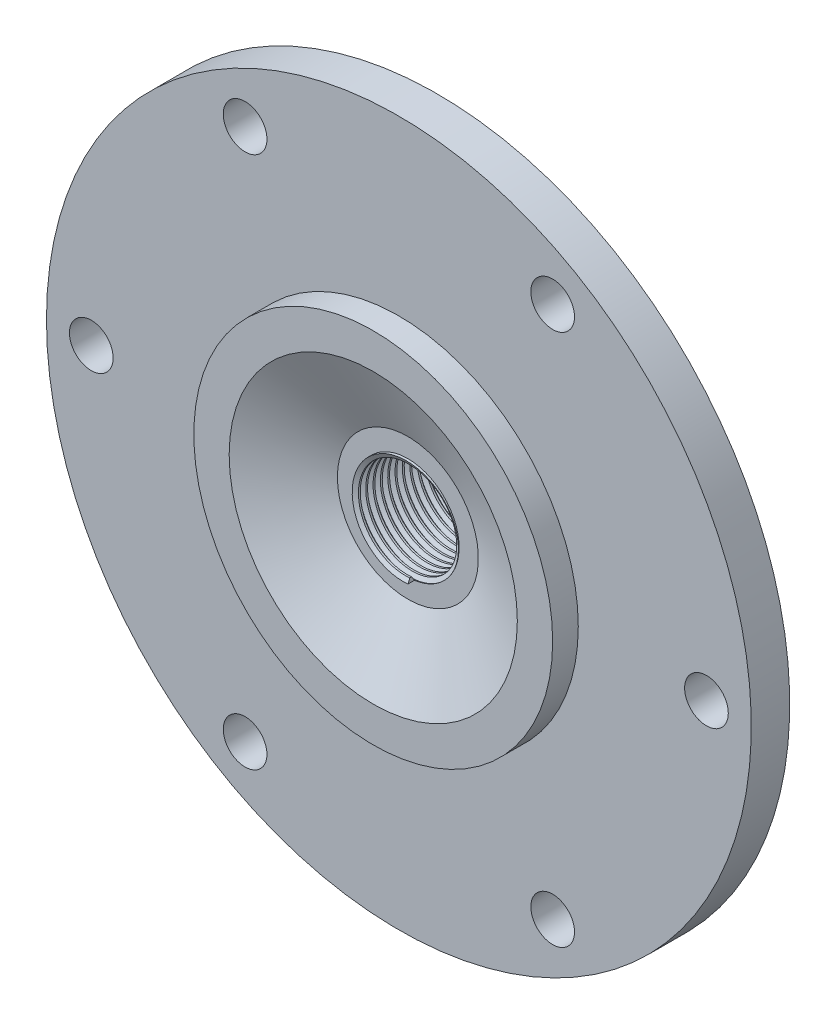
SolidWorks part; units mm, degrees
ref_plane "Front Plane" through (0, 0, 0) normal (0, 0, 1) x (1, 0, 0)
ref_plane "Top Plane" through (0, 0, 0) normal (0, 1, 0) x (1, 0, 0)
ref_plane "Right Plane" through (0, 0, 0) normal (1, 0, 0) x (0, 0, -1)
sketch "Sketch1" plane through (0, 0, 0) normal (0, 0, 1) x (1, 0, 0)
  circle A0 centre (0, 0) radius 43.6562
extrude "Boss-Extrude1" add sketch "Sketch1" along normal blind 4.7625
sketch "Sketch2" plane through (0, 0, 4.7625) normal (0, 0, 1) x (1, 0, 0)
  circle A0 centre (0, 0) radius 22.225
extrude "Boss-Extrude2" add sketch "Sketch2" along normal blind 3.175
sketch "Sketch3" plane through (0, 0, 0) normal (0, 0, -1) x (-1, 0, 0)
  circle A0 centre (0, 0) radius 9.525
extrude "Boss-Extrude3" add sketch "Sketch3" along normal blind 14.2875
chamfer "Chamfer1" distance 6.35 angle 30 1 edges at (-9.525, 0, 0)
sketch "Sketch4" plane through (0, 0, 0) normal (0, 1, 0) x (1, 0, 0)
  line L0 (0, -3.6471) -> (-8.7312, -3.6471)
  line L1 (-8.7312, -3.6471) -> (-17.8484, -7.9375)
  line L2 (0, -3.6471) -> (0, -7.9375)
  line L3 (-22.225, -7.9375) -> (22.225, -7.9375) construction
  line L4 (0, -7.9375) -> (-17.8484, -7.9375)
  dimension "D1" = 8.7312
revolve "Cut-Revolve1" cut sketch "Sketch4" angle 360 about L2
sketch "Sketch5" plane through (0, 0, -14.2875) normal (0, 0, -1) x (-1, 0, 0)
  circle A0 centre (0, 0) radius 6.35
  dimension "D1" = 12.7
hole_wizard "#3 (0.213) Diameter Hole1" positions "3DSketch1" profile "Sketch6" hole size "#3" standard "ANSI Inch"
sketch3d "3DSketch1"
  line L0 (0, 0, 0) -> (0, 49.4218, 0) construction
  line L1 (0, 49.4218, 0) -> (0, 0, 0) construction
  line L2 (0, 0, 0) -> (-50.2908, 0, 0) construction
  line L4 (0, 0, 0) -> (19.05, 32.9956, 0) construction
  point P14 (-38.6618, 0, 0)
  point P16 (-35.677, 0, 0)
  point P27 (-38.6618, 0, 0)
  point P29 (-35.677, 0, 0)
  point P31 (-29.7925, 0, 0)
  point P33 (-1.7965, 0, 0)
  point P35 (38.1, 0, 0)
  point P38 (-38.1, 0, 0)
  point P43 (20.1397, 34.8829, 0)
  point P49 (19.05, 32.9956, 0)
  point P56 (19.05, -32.9956, 0)
  point P57 (0, 0, 0)
  point P58 (-19.05, -32.9956, 0)
  point P59 (-19.05, 32.9956, 0)
  dimension "D3" = 0
  dimension "D4" = 38.1
sketch "Sketch6" plane through (-19.05, 32.9956, 0) normal (1, 0, 0) x (0, 1, 0)
  line L0 (0, 0) -> (0, 4.7635)
  line L1 (0, 4.7635) -> (2.7051, 4.7635)
  line L2 (2.7051, 4.7635) -> (2.7051, 0)
  line L5 (2.7051, 0) -> (0, 0)
  line L11 (0, -6.35) -> (0, 107.95) construction
  dimension "Thru Hole Dia." = 5.4102
  dimension "Thru Hole Depth" = 4.7635
extrude "Cut-Extrude1" cut sketch "Sketch5" against normal up to next
thread "Thread1" pitch 0.9071 start angle 0, offset 0, length 0, pitch 0.9071, diameter 12.7
ref_plane "Plane1" through (6.35, 0, -14.2875) normal (0, -1, 0) x (1, 0, 0)
sketch "Thread Profile1" plane through (6.35, 0, -14.2875) normal (0, -1, 0) x (1, 0, 0)
  line L0 (0, 0) -> (0, 0.9071) construction
  line L11 (0, 0) -> (0, 0.7937)
  line L12 (0, 0.7937) -> (-0.491, 0.5103)
  line L13 (-0.491, 0.5103) -> (-0.491, 0.2835)
  line L15 (-0.491, 0.2835) -> (0, 0)
  line L17 (-0.491, 0.3969) -> (0, 0.3969) construction
  point P2 (0, 0)
  dimension "Pitch" = 0.9071
  dimension "Profile_Angle" = 60
  dimension "Profile_Land" = 0.2268
  dimension "Profile_Height" = 0.491
